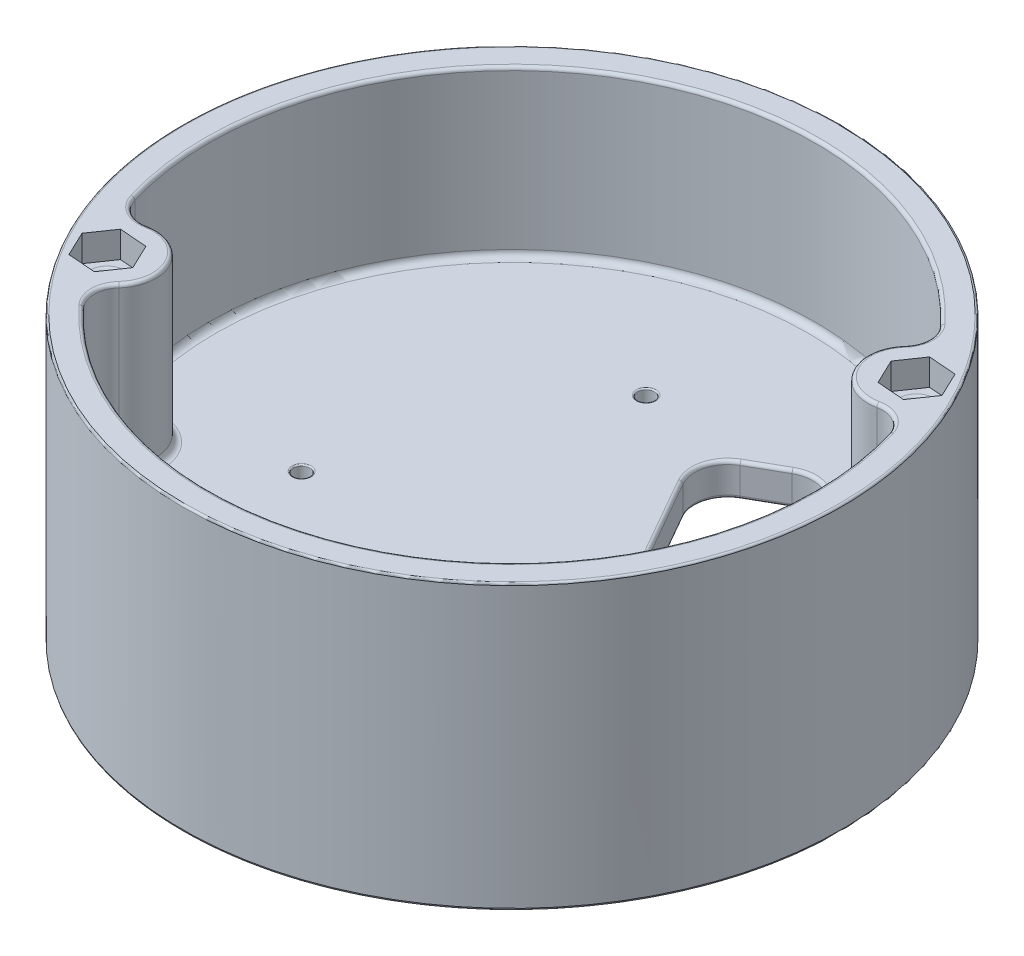
SolidWorks part; units mm, degrees
ref_plane "Front Plane" through (0, 0, 0) normal (0, 0, 1) x (1, 0, 0)
ref_plane "Top Plane" through (0, 0, 0) normal (0, 1, 0) x (1, 0, 0)
ref_plane "Right Plane" through (0, 0, 0) normal (1, 0, 0) x (0, 0, -1)
sketch "Sketch1" plane through (0, 0, 0) normal (0, 1, 0) x (1, 0, 0)
  circle A0 centre (0, 0) radius 50
  point P0 (0, 0)
  dimension "D1" = 100
extrude "Boss-Extrude1" add sketch "Sketch1" along normal blind 5
sketch "Sketch3" plane through (0, 5, 0) normal (0, 1, 0) x (1, 0, 0)
  line L0 (9.8089, 16.1295) -> (18.1373, 1.5273)
  line L1 (24.9577, -0.3388) -> (29.9775, 2.5243)
  line L2 (31.8436, 9.3447) -> (23.5152, 23.9468)
  line L3 (16.6948, 25.8129) -> (11.675, 22.9499)
  circle A4 centre (18.9913, -16.1068) radius 1.25
  circle A5 centre (-20.3263, -11.5931) radius 1.25
  circle A6 centre (-4.1949, 24.5458) radius 1.2779
  arc A7 (29.9775, 2.5243) -> (31.8436, 9.3447) centre (27.5003, 6.8675) ccw
  arc A8 (18.1373, 1.5273) -> (24.9577, -0.3388) centre (22.4805, 4.0045) ccw
  arc A9 (9.8089, 16.1295) -> (11.675, 22.9499) centre (14.1522, 18.6066) cw
  arc A10 (23.5152, 23.9468) -> (16.6948, 25.8129) centre (19.172, 21.4697) ccw
  point P12 (-1.7935, -2.0357)
  dimension "D1" = 5
extrude "Cut-Extrude2" cut sketch "Sketch3" against normal blind 50
sketch "Sketch2" plane through (0, 5, 0) normal (0, 1, 0) x (1, 0, 0)
  line L0 (0, 0) -> (-20.3263, -11.5931) construction
  arc A0 (-36.782, -27.624) -> (42.5018, 17.5954) centre (0, 0) ccw
  circle A1 centre (0, 0) radius 50
  circle A2 centre (0, 0) radius 50
  arc A3 (36.782, 27.624) -> (42.5018, 17.5954) centre (38.2205, 21.799) ccw
  arc A4 (-36.782, -27.624) -> (-42.5018, -17.5954) centre (-38.2205, -21.799) ccw
  circle A5 centre (0, 0) radius 46 construction
  arc A6 (36.782, 27.624) -> (-42.5018, -17.5954) centre (0, 0) ccw
  dimension "D3" = 12
  dimension "D4" = 12
  dimension "D1" = 0
  dimension "D2" = 4
extrude "Boss-Extrude2" add sketch "Sketch2" along normal blind 25
sketch "Sketch4" plane through (0, 30, 0) normal (0, 1, 0) x (1, 0, 0)
  circle A1 centre (39.0891, 22.2944) radius 2.25
  circle A3 centre (-39.0891, -22.2944) radius 2.25
  dimension "D1" = 4.5
  dimension "D2" = 4.5
extrude "Cut-Extrude3" cut sketch "Sketch4" against normal through all
sketch "Sketch5" plane through (0, 30, 0) normal (0, 1, 0) x (1, 0, 0)
  line L12 (37.2797, 26.0877) -> (34.8994, 22.6241)
  line L13 (34.8994, 22.6241) -> (36.7087, 18.8309)
  line L14 (36.7087, 18.8309) -> (40.8985, 18.5012)
  line L15 (40.8985, 18.5012) -> (43.2788, 21.9648)
  line L16 (43.2788, 21.9648) -> (41.4695, 25.758)
  line L17 (41.4695, 25.758) -> (37.2797, 26.0877)
  line L18 (-40.8973, -18.5036) -> (-43.2762, -21.965)
  line L19 (-43.2762, -21.965) -> (-41.468, -25.7558)
  line L20 (-41.468, -25.7558) -> (-37.2809, -26.0853)
  line L21 (-37.2809, -26.0853) -> (-34.902, -22.6239)
  line L22 (-34.902, -22.6239) -> (-36.7102, -18.8331)
  line L23 (-36.7102, -18.8331) -> (-40.8973, -18.5036)
extrude "Cut-Extrude4" cut sketch "Sketch5" against normal blind 4
sketch "Sketch6" plane through (0, 0, 0) normal (0, -1, 0) x (1, 0, 0)
  circle A5 centre (39.0891, -22.2944) radius 2.25 construction
  circle A6 centre (0, 0) radius 50
  circle A7 centre (-39.0891, 22.2944) radius 2.25 construction
  arc A8 (-43.2814, 19.5696) -> (38.8781, -27.29) centre (0, 0) ccw
  arc A9 (43.2814, -19.5696) -> (38.8781, -27.29) centre (39.0891, -22.2944) ccw
  arc A10 (43.2814, -19.5696) -> (-38.8781, 27.29) centre (0, 0) ccw
  arc A11 (-43.2814, 19.5696) -> (-38.8781, 27.29) centre (-39.0891, 22.2944) ccw
  circle A12 centre (39.0891, -22.2944) radius 2.25
  circle A13 centre (-39.0891, 22.2944) radius 2.25
  dimension "D1" = 5
  dimension "D2" = 5
  dimension "D3" = 47.5
  dimension "D4" = 100
extrude "Boss-Extrude3" add sketch "Sketch6" along normal blind 13
fillet "Fillet1" radius 4 4 edges at (43.2814, -6.5, -19.5696) (38.8781, -6.5, -27.29) (-43.2814, -6.5, 19.5696) (-38.8781, -6.5, 27.29)
fillet "Fillet2" radius 0.5 8 edges at (43.2483, -13, -17.0854) (34.7459, -13, -19.8173) (36.723, -13, -28.5262) (-23.533, -13, -41.2607) (-43.2483, -13, 17.0854) (-34.7459, -13, 19.8173) (-36.723, -13, 28.5262) (23.533, -13, 41.2607)
fillet "Fillet3" radius 0.8 8 edges at (43.2483, 0, -17.0854) (34.7459, 0, -19.8173) (36.723, 0, -28.5262) (-23.533, 0, -41.2607) (-43.2483, 0, 17.0854) (-34.7459, 0, 19.8173) (-36.723, 0, 28.5262) (23.533, 0, 41.2607)
fillet "Fillet4" radius 0.3 2 edges at (0, 30, 50) (0, -13, -50)
fillet "Fillet5" radius 4 4 edges at (42.5018, 17.5, -17.5954) (36.782, 17.5, -27.624) (-36.782, 17.5, 27.624) (-42.5018, 17.5, 17.5954)
fillet "Fillet6" radius 0.5 10 edges at (-34.8238, 30, 28.5458) (-33.0086, 30, 18.8264) (-42.2983, 30, 15.4407) (-22.7899, 30, -39.9578) (34.8238, 30, -28.5458) (33.0086, 30, -18.8264) (42.2983, 30, -15.4407) (22.7899, 30, 39.9578) (-39.0891, 26, 24.5444) (39.0891, 26, -20.0444)
fillet "Fillet7" radius 1 8 edges at (-34.8238, 5, 28.5458) (-33.0086, 5, 18.8264) (-42.2983, 5, 15.4407) (-22.7899, 5, -39.9578) (34.8238, 5, -28.5458) (33.0086, 5, -18.8264) (42.2983, 5, -15.4407) (22.7899, 5, 39.9578)
fillet "Fillet8" radius 0.5 16 edges at (32.3231, 0, -5.548) (27.4676, 0, -1.0928) (21.161, 0, 0.8183) (13.9731, 0, -8.8284) (9.3294, 0, -19.9261) (14.1849, 0, -24.3814) (20.4915, 0, -26.2924) (32.3231, 5, -5.548) (27.4676, 5, -1.0928) (21.161, 5, 0.8183) (13.9731, 5, -8.8284) (9.3294, 5, -19.9261) (14.1849, 5, -24.3814) (20.4915, 5, -26.2924) (27.6794, 0, -16.6458) (27.6794, 5, -16.6458)
fillet "Fillet9" radius 0.2 6 edges at (-4.1949, 0, -23.2679) (-4.1949, 5, -23.2679) (-20.3263, 0, 12.8431) (-20.3263, 5, 12.8431) (18.9913, 0, 17.3568) (18.9913, 5, 17.3568)
